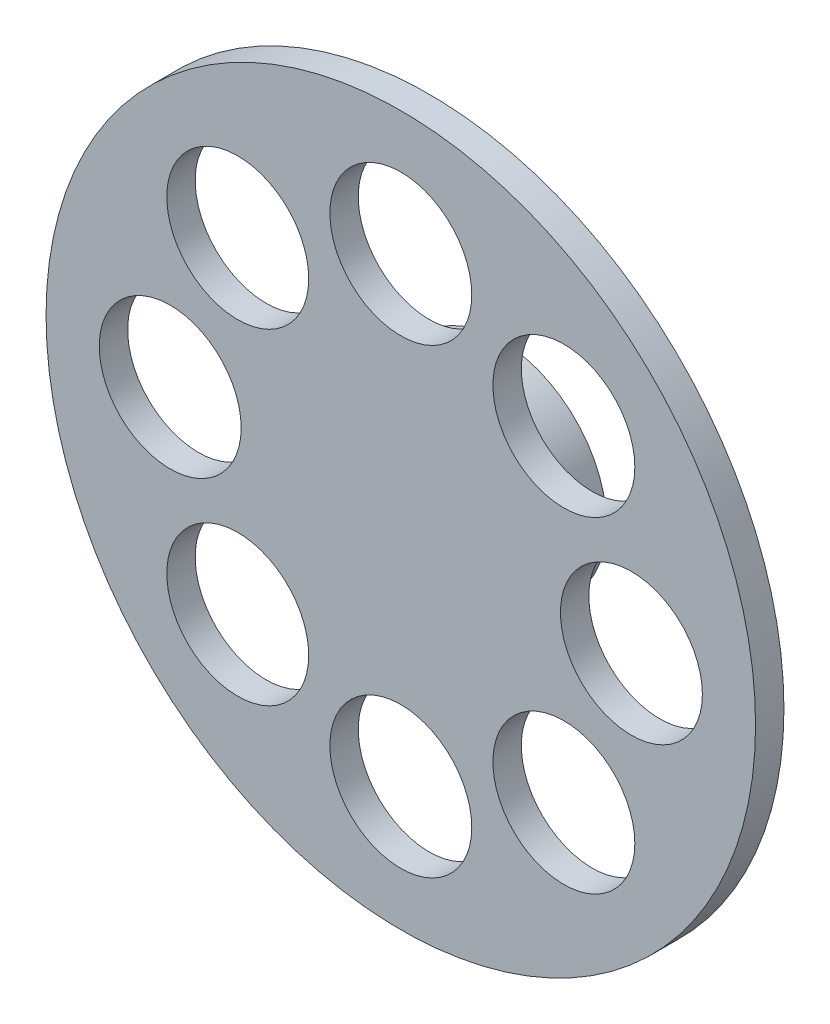
SolidWorks part; units mm, degrees
ref_plane "Plano frontal" through (0, 0, 0) normal (0, 0, 1) x (1, 0, 0)
ref_plane "Plano superior" through (0, 0, 0) normal (0, 1, 0) x (1, 0, 0)
ref_plane "Plano direito" through (0, 0, 0) normal (1, 0, 0) x (0, 0, -1)
sketch "Esboço1" plane through (0, 0, 0) normal (0, 0, 1) x (1, 0, 0)
  line L0 (0, 4.9) -> (0, 6.5) construction
  line L1 (0.9, 6.4374) -> (0.9, 4.8166) construction
  line L2 (-0.9, 6.4374) -> (-0.9, 4.8166) construction
  line L3 (0.89, 6.4388) -> (0.89, 4.8185) construction
  line L4 (-0.89, 6.4388) -> (-0.89, 4.8185) construction
  line L5 (0.89, 8.5) -> (0.89, 9.4412) construction
  line L6 (0.9, 8.5) -> (0.9, 9.4412) construction
  line L7 (-0.9, 8.5) -> (-0.9, 9.4412) construction
  line L8 (-0.89, 8.5) -> (-0.89, 9.4412) construction
  line L9 (0.89, 6.4388) -> (0.9, 4.8166)
  line L10 (0, 8.5) -> (0, 9.4412) construction
  line L11 (-0.89, 6.4388) -> (-0.9, 4.8166)
  arc A0 (0.89, 6.4388) -> (-0.89, 6.4388) centre (0, 0) ccw
  circle A1 centre (0, 0) radius 4.9
  circle A2 centre (0, 0) radius 7.5
  point P22 (0, 0)
  point P23 (1, 4.3875)
  point P24 (2.6047, 8.7753)
  point P25 (-1, 6.8072)
  point P26 (0, 0)
  point P27 (-1.5, 6.5809)
  point P28 (0, 4.5)
  point P30 (0, 0)
  point P31 (-1, 6.4226)
  point P32 (-1.5, 4.2426)
  point P33 (0, 0)
  point P34 (0, 9.0283)
  point P35 (1.5, 4.2426)
  point P36 (0, 0)
  point P37 (1, 6.4226)
  point P38 (0, 9.4412)
  dimension "D1" = 0.9
  dimension "D5" = 9.8
  dimension "D6" = 6.5
  dimension "D7" = 15
  dimension "D2" = 0.9
  dimension "D3" = 0.89
  dimension "D4" = 0.89
extrude "Ressalto-extrusão1" add sketch "Esboço1" along normal blind 5 contours A2 A1 L11 A0 L9 | A1 L9 A0 L11 region at (0, 5.6744, 0) region at (-7.2879, 0, 0)
extrude "Corte-extrusão1" cut sketch "Esboço1<3>" along normal blind 5 contours A1 L9 A0 L11 region at (0, 5.6744, 0)
sketch "Esboço1<3>" plane through (0, 0, 0) normal (0, 0, 1) x (1, 0, 0) same geometry as "Esboço1"
pattern_circular "PadrãoCircular2" count 14 over 360 about axis through (0, 0, 5) along (0, 0, -1) of "Corte-extrusão1"
sketch "Esboço2" plane through (0, 0, 5) normal (0, 0, 1) x (1, 0, 0)
  line L0 (0, 7.5) -> (0, 25) construction
  circle A0 centre (0, 0) radius 25
  circle A1 centre (0, 16.25) radius 5
  circle A2 centre (0, 0) radius 7.5 construction
  circle A3 centre (11.4905, 11.4905) radius 5
  circle A4 centre (16.25, 0) radius 5
  circle A5 centre (11.4905, -11.4905) radius 5
  circle A6 centre (0, -16.25) radius 5
  circle A7 centre (-11.4905, -11.4905) radius 5
  circle A8 centre (-16.25, 0) radius 5
  circle A9 centre (-11.4905, 11.4905) radius 5
  point P26 (0, 0)
  dimension "D1" = 8
extrude "Ressalto-extrusão2" add sketch "Esboço2" along normal blind 2
